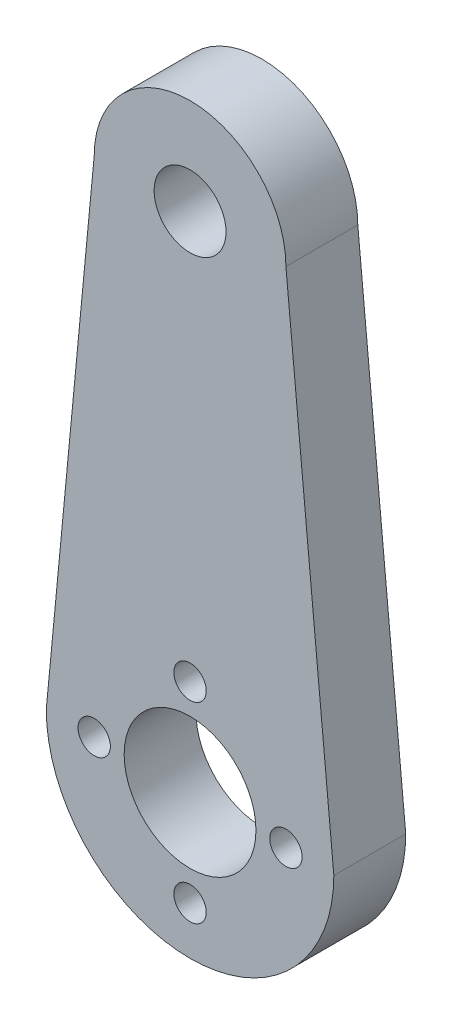
SolidWorks part; units mm, degrees
ref_plane "Front" through (0, 0, 0) normal (0, 0, 1) x (1, 0, 0)
ref_plane "Top" through (0, 0, 0) normal (0, 1, 0) x (1, 0, 0)
ref_plane "Right" through (0, 0, 0) normal (1, 0, 0) x (0, 0, -1)
sketch "Esquisse1" plane through (0, 0, 0) normal (0, 0, 1) x (1, 0, 0)
  line L0 (0, 0) -> (0, 42) construction
  line L1 (12, 0) -> (8, 42)
  line L2 (0, 58) -> (0, 42) construction
  line L3 (0, -12) -> (0, 0) construction
  line L4 (12, 0) -> (-12, 0) construction
  line L5 (8, 42) -> (-8, 42) construction
  line L6 (-12, 0) -> (-8, 42)
  arc A0 (8, 42) -> (-8, 42) centre (0, 42) ccw
  arc A1 (12, 0) -> (-12, 0) centre (0, 0) cw
  dimension "D2" = 12
  dimension "D3" = 8
  dimension "D1" = 42
extrude "Boss.-Extru.1" add sketch "Esquisse1" along normal blind 6
sketch "Esquisse2" plane through (0, 0, 6) normal (0, 0, 1) x (1, 0, 0)
  line L0 (0, 0) -> (8, 0) construction
  circle A0 centre (0, 0) radius 5.5
  circle A1 centre (8, 0) radius 1.35
  circle A2 centre (0, -8) radius 1.35
  circle A3 centre (-8, 0) radius 1.35
  circle A4 centre (0, 8) radius 1.35
  circle A5 centre (0, 42) radius 3
  point P14 (0, 0)
  dimension "D1" = 11
  dimension "D2" = 2.7
  dimension "D5" = 6
  dimension "D3" = 8
  dimension "D4" = 4
extrude "Enlèv. mat.-Extru.1" cut sketch "Esquisse2" against normal through all both and the other way through all
